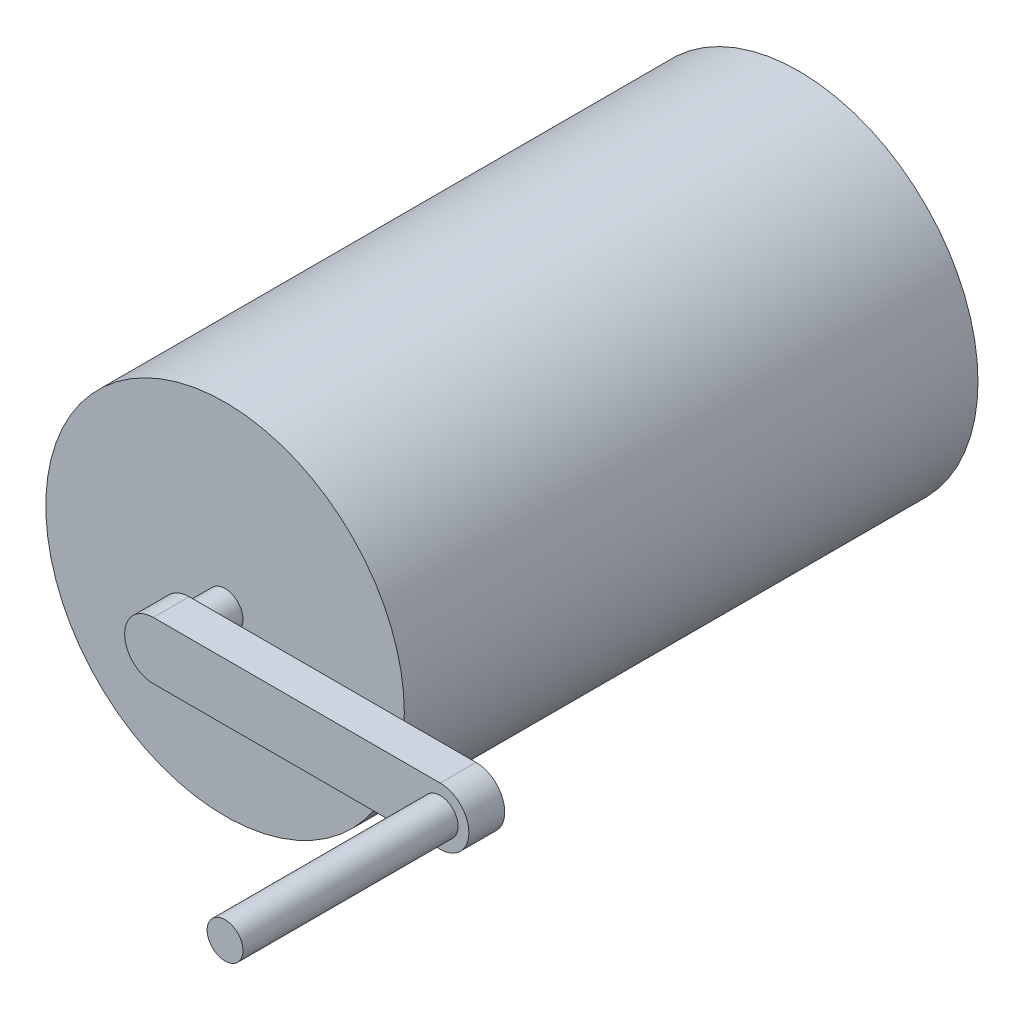
SolidWorks part; units mm, degrees
ref_plane "Front Plane" through (0, 0, 0) normal (0, 0, 1) x (1, 0, 0)
ref_plane "Top Plane" through (0, 0, 0) normal (0, 1, 0) x (1, 0, 0)
ref_plane "Right Plane" through (0, 0, 0) normal (1, 0, 0) x (0, 0, -1)
sketch "Sketch1" plane through (0, 0, 0) normal (0, 0, 1) x (1, 0, 0)
  circle A0 centre (0, 0) radius 15.875
  dimension "D1" = 31.75
extrude "Boss-Extrude1" add sketch "Sketch1" along normal blind 50.8
sketch "Sketch2" plane through (0, 0, 50.8) normal (0, 0, 1) x (1, 0, 0)
  circle A0 centre (0, 0) radius 1.5875
  dimension "D1" = 3.175
extrude "Boss-Extrude2" add sketch "Sketch2" along normal blind 6.35
sketch "Sketch3" plane through (0, 0, 57.15) normal (0, 0, 1) x (1, 0, 0)
  line L0 (0, 2.54) -> (25.4, 2.54)
  line L1 (0, -2.54) -> (25.4, -2.54)
  arc A0 (0, 2.54) -> (0, -2.54) centre (0, 0) ccw
  arc A1 (25.4, -2.54) -> (25.4, 2.54) centre (25.4, 0) ccw
  dimension "D1" = 5.08
  dimension "D2" = 25.4
extrude "Boss-Extrude3" add sketch "Sketch3" against normal blind 3.175
sketch "Sketch4" plane through (0, 0, 57.15) normal (0, 0, 1) x (1, 0, 0)
  circle A0 centre (25.4, 0) radius 1.5875
  dimension "D1" = 3.175
extrude "Boss-Extrude4" add sketch "Sketch4" along normal blind 19.05
